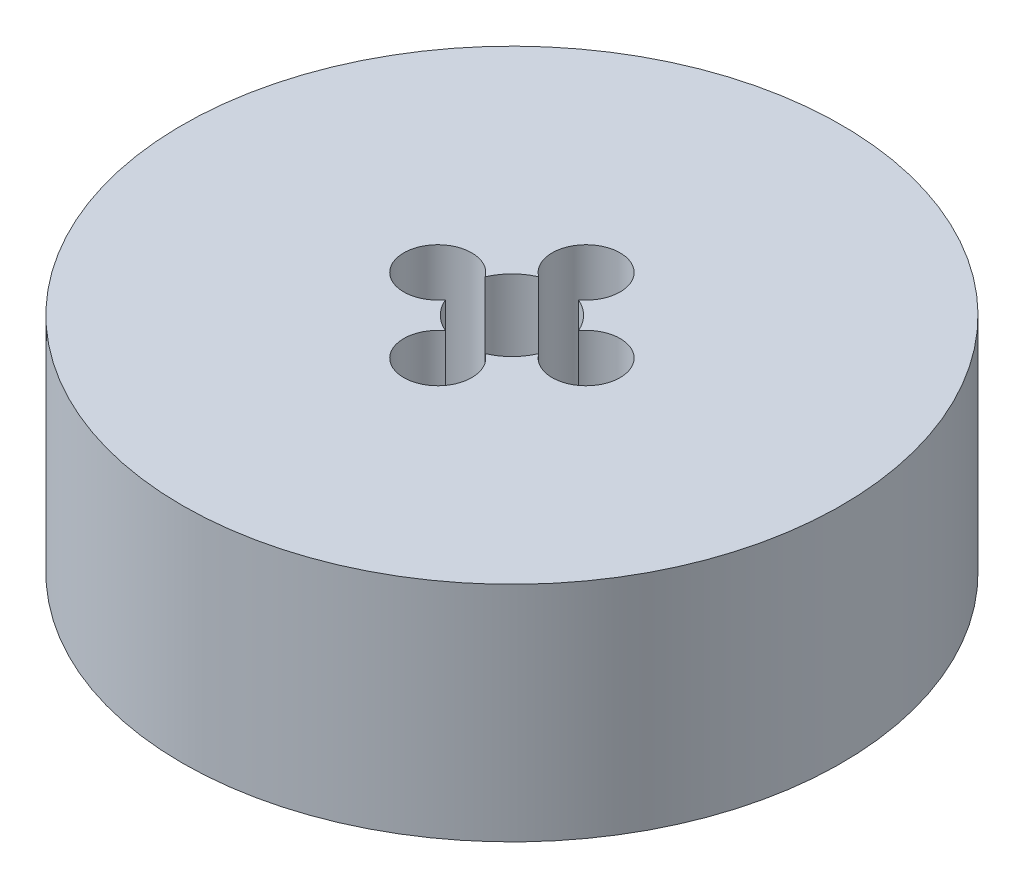
SolidWorks part; units mm, degrees
ref_plane "Front Plane" through (0, 0, 0) normal (0, 0, 1) x (1, 0, 0)
ref_plane "Top Plane" through (0, 0, 0) normal (0, 1, 0) x (1, 0, 0)
ref_plane "Right Plane" through (0, 0, 0) normal (1, 0, 0) x (0, 0, -1)
sketch "Sketch1" plane through (0, 0, 0) normal (0, 1, 0) x (1, 0, 0)
  circle A0 centre (0, 0) radius 32.5
  dimension "FLANGE_OD" = 65
extrude "Boss-Extrude1" add sketch "Sketch1" along normal blind 22
sketch "Sketch2" plane through (0, 0, 0) normal (0, 1, 0) x (1, 0, 0)
  circle A0 centre (0, 0) radius 5
  dimension "BORE_D" = 10
extrude "Cut-Extrude1" cut sketch "Sketch2" along normal through all
sketch "Sketch3" plane through (0, 22, 0) normal (0, 1, 0) x (1, 0, 0)
  circle A0 centre (0, 0) radius 7.3157 construction
  circle A1 centre (-7.3157, 0) radius 3.3493
  dimension "BOLT_D" = 6.6985
  dimension "BOLT_PCD" = 14.6313
extrude "Cut-Extrude2" cut sketch "Sketch3" against normal blind 18.8049
pattern_circular "CirPattern1" count 4 over 360 about axis through (0, 0, 0) along (0, 1, 0) of "Cut-Extrude2"
